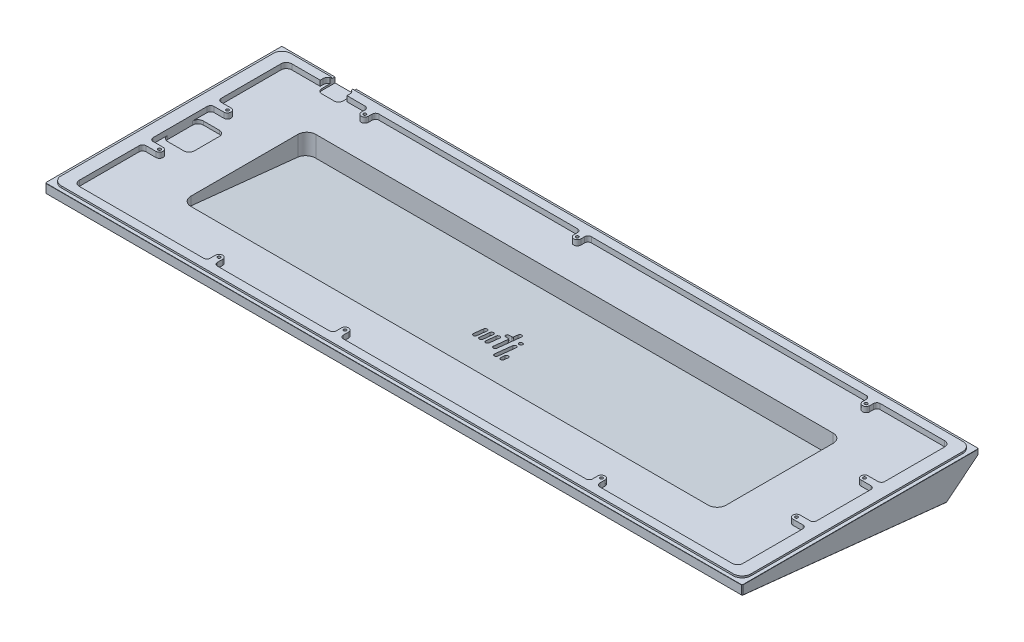
SolidWorks part; units mm, degrees
material "6061-T6 (SS)"
ref_plane "Front Plane" through (0, 0, 0) normal (0, 0, 1) x (1, 0, 0)
ref_plane "Top Plane" through (0, 0, 0) normal (0, 1, 0) x (1, 0, 0)
ref_plane "Right Plane" through (0, 0, 0) normal (1, 0, 0) x (0, 0, -1)
sketch "Sketch1" plane through (0, 0, 0) normal (0, 1, 0) x (1, 0, 0)
  line L1 (0, 0) -> (390.7, 0)
  line L2 (0, 0) -> (0, 132.7)
  line L3 (0, 132.7) -> (390.7, 132.7)
  line L4 (390.7, 0) -> (390.7, 132.7)
  dimension "D1" = 390.7
  dimension "D2" = 132.7
extrude "MainBody" add sketch "Sketch1" along normal blind 18.5
sketch "Sketch2" plane through (0, 18.5, 0) normal (0, 1, 0) x (1, 0, 0)
  line L0 (390.7, 132.7) -> (0, 132.7) construction
  line L1 (2.05, 130.65) -> (388.65, 130.65)
  line L2 (2.05, 130.65) -> (2.05, 2.05)
  line L3 (2.05, 2.05) -> (388.65, 2.05)
  line L4 (388.65, 130.65) -> (388.65, 2.05)
  line L5 (0, 132.7) -> (0, 0) construction
  line L7 (0, 132.7) -> (390.7, 132.7)
  line L8 (0, 132.7) -> (0, 0)
  line L9 (0, 0) -> (390.7, 0)
  line L10 (390.7, 132.7) -> (390.7, 0)
  point P4 (195.35, 130.65)
  point P7 (195.35, 132.7)
  point P8 (2.05, 66.35)
  point P11 (0, 66.35)
  line M5 (0, 132.7) -> (0, 0)
  line M6 (0, 0) -> (390.7, 0)
  line M7 (390.7, 0) -> (390.7, 132.7)
  line M8 (390.7, 132.7) -> (0, 132.7)
  dimension "D1" = 2.05
  dimension "D2" = 2.05
extrude "AligmentLip" cut sketch "Sketch2" against normal blind 1 contours L1 L4 L3 L2 M8 M5 M6 M7
sketch "Sketch3" plane through (0, 0, 0) normal (-1, 0, 0) x (0, 0, 1)
  line L0 (-132.7, 14.5) -> (-114.794, 0)
  line L1 (-132.7, 17.5) -> (-132.7, 0) construction
  line L2 (-132.7, 0) -> (0, 0) construction
  line L3 (-114.794, 0) -> (0, 12.0653)
  line L4 (0, 17.5) -> (0, 0) construction
  line L5 (-132.7, 17.5) -> (0, 17.5) construction
  line L7 (-132.7, 17.5) -> (0, 17.5)
  line L8 (-132.7, 17.5) -> (-132.7, 0)
  line L9 (-132.7, 0) -> (0, 0)
  line L10 (0, 17.5) -> (0, 0)
  line M4 (-132.7, 17.5) -> (-132.7, 0)
  line M5 (-132.7, 0) -> (0, 0)
  line M6 (0, 0) -> (0, 17.5)
  dimension "D1" = 6
  dimension "D2" = 135
  dimension "D3" = 3
extrude "TypingAngle" cut sketch "Sketch3" against normal through all contours L0 M4 M5 | L3 M5 M6
sketch "Sketch4" plane through (0, 18.5, 0) normal (0, 1, 0) x (1, 0, 0)
  line L0 (2.05, 130.65) -> (388.65, 130.65) construction
  line L1 (9.35, 125.9) -> (381.35, 125.9)
  line L2 (9.35, 125.9) -> (9.35, 6.8)
  line L3 (9.35, 6.8) -> (381.35, 6.8)
  line L4 (381.35, 125.9) -> (381.35, 6.8)
  line L5 (2.05, 130.65) -> (2.05, 2.05) construction
  point P4 (195.35, 125.9)
  point P7 (195.35, 130.65)
  point P8 (9.35, 66.35)
  point P11 (2.05, 66.35)
  dimension "D1" = 372
  dimension "D2" = 119.1
extrude "PCBCutout" cut sketch "Sketch4" against normal blind 3
sketch "Sketch13" plane through (0, 15.5, 0) normal (0, 1, 0) x (1, 0, 0)
  line L0 (9.35, 125.9) -> (9.35, 6.8) construction
  line L1 (9.35, 76.35) -> (24.35, 76.35)
  line L2 (9.35, 76.35) -> (9.35, 56.35)
  line L3 (9.35, 56.35) -> (24.35, 56.35)
  line L4 (24.35, 76.35) -> (24.35, 56.35)
  line L5 (2.05, 130.65) -> (2.05, 2.05) construction
  point P6 (9.35, 66.35)
  point P9 (2.05, 66.35)
  dimension "D1" = 15
  dimension "D2" = 20
extrude "Cut-Extrude4" cut sketch "Sketch13" against normal blind 2
fillet "Fillet2" radius 3 8 edges at (381.35, 17, -125.9) (381.35, 17, -6.8) (9.35, 17, -6.8) (9.35, 17, -125.9) (9.35, 14.5, -56.35) (24.35, 14.5, -56.35) (9.35, 14.5, -76.35) (24.35, 14.5, -76.35)
chamfer "Chamfer1" distance 0.5 angle 45 13 edges at (195.35, 12.0653, 0) (390.7, 16, -132.7) (0, 16, -132.7) (0, 7.25, -123.747) (390.7, 7.25, -123.747) (390.7, 6.0327, -57.397) (390.7, 14.7827, 0) (0, 6.0327, -57.397) (0, 14.7827, 0) (0, 17.5, -66.35) (195.35, 17.5, 0) (390.7, 17.5, -66.35) (195.35, 17.5, -132.7)
chamfer "Chamfer2" distance 0.1 angle 45 1 edges at (2.05, 18.5, -66.35)
sketch "Sketch17" plane through (0, 11.9335, -1.2543) normal (0, -0.9945, 0.1045) x (1, 0, 0)
  line L0 (198.25, -60.7388) -> (196.25, -60.7388) construction
  line L1 (198.25, -68.7388) -> (196.25, -68.7388)
  line L2 (198.25, -68.7388) -> (198.25, -52.7388)
  line L3 (198.25, -52.7388) -> (196.25, -52.7388)
  line L4 (196.25, -68.7388) -> (196.25, -52.7388)
  line L5 (202.75, -61.2388) -> (200.75, -61.2388)
  line L6 (202.75, -61.2388) -> (202.75, -48.7388)
  line L7 (202.75, -48.7388) -> (200.75, -48.7388)
  line L8 (200.75, -61.2388) -> (200.75, -48.7388)
  line L9 (193.45, -61.2388) -> (191.45, -61.2388)
  line L10 (193.45, -61.2388) -> (193.45, -53.2388)
  line L11 (193.45, -53.2388) -> (191.45, -53.2388)
  line L12 (191.45, -61.2388) -> (191.45, -53.2388)
  line L13 (189.95, -61.2388) -> (187.95, -61.2388)
  line L14 (189.95, -61.2388) -> (189.95, -53.2388)
  line L15 (189.95, -53.2388) -> (187.95, -53.2388)
  line L16 (187.95, -61.2388) -> (187.95, -53.2388)
  line L17 (186.45, -61.2388) -> (184.45, -61.2388)
  line L18 (186.45, -61.2388) -> (186.45, -53.2388)
  line L19 (186.45, -53.2388) -> (184.45, -53.2388)
  line L20 (184.45, -61.2388) -> (184.45, -53.2388)
  line L25 (202.75, -61.2388) -> (187.95, -61.2388) construction
  line L26 (390.2, -114.1651) -> (0.5, -114.1651) construction
  line L27 (194.25, -64.7388) -> (198.25, -64.7388)
  line L28 (194.25, -62.7388) -> (198.25, -62.7388)
  line L29 (390.7, 1.2612) -> (0, 1.2612) construction
  line L31 (206.25, -53.2388) -> (204.25, -53.2388)
  line L32 (206.25, -53.2388) -> (206.25, -48.7388)
  line L33 (206.25, -48.7388) -> (204.25, -48.7388)
  line L34 (204.25, -53.2388) -> (204.25, -48.7388)
  circle A0 centre (201.75, -63.7388) radius 1
  circle A2 centre (194.25, -63.7388) radius 1
  circle A3 centre (197.25, -67.7388) radius 1
  circle A4 centre (197.25, -53.7388) radius 1
  circle A5 centre (201.75, -60.2388) radius 1
  circle A6 centre (201.75, -49.7388) radius 1
  circle A7 centre (205.25, -52.2388) radius 1
  circle A8 centre (205.25, -49.7388) radius 1
  circle A9 centre (192.45, -60.2388) radius 1
  circle A10 centre (192.45, -54.2388) radius 1
  circle A11 centre (188.95, -60.2388) radius 1
  circle A12 centre (188.95, -54.2388) radius 1
  circle A13 centre (185.45, -60.2388) radius 1
  circle A14 centre (185.45, -54.2388) radius 1
  point P28 (195.35, -61.2388)
  point P29 (201.75, -61.2388)
  point P31 (0, 0)
  point P33 (195.35, -114.1651)
  point P44 (197.25, -68.7388)
  dimension "D12" = 2
  dimension "D13" = 12.5
  dimension "D16" = 2
  dimension "D1" = 16
  dimension "D2" = 2
  dimension "D3" = 0
  dimension "D4" = 2.5
  dimension "D5" = 2.8
  dimension "D6" = 1.5
  dimension "D7" = 1.5
  dimension "D8" = 8
  dimension "D9" = 0.5
  dimension "D10" = 1.5
  dimension "D11" = 2.5
  dimension "D14" = 4.5
  dimension "D15" = 50
  dimension "D17" = 2
  dimension "D18" = 3
  dimension "D19" = 11
extrude "Cut-Extrude5" cut sketch "Sketch17" against normal blind 10 contours A7 | A8 L34 A7 L32 | A8 | A6 | A6 L8 A5 L6 | A5 | A4 | A4 L4 L28 L2 | L28 L4 L27 L2 | A3 L2 L27 L4 | A3 | A2 L27 L4 L28 | A2 | A0 | A9 | A10 L12 A9 L10 | A10 | A12 L16 A11 L14 | A11 | A12 | A14 | A14 L20 A13 L18 | A13
sketch "Sketch18" plane through (0, 0, -132.7) normal (0, 0, -1) x (-1, 0, 0)
  line L1 (-41.8, 18.5) -> (-29.8, 18.5)
  line L2 (-41.8, 18.5) -> (-41.8, 14.5)
  line L3 (-41.8, 14.5) -> (-29.8, 14.5)
  line L4 (-29.8, 18.5) -> (-29.8, 14.5)
  line L5 (0, 17.5) -> (0, 14.7385) construction
  line L6 (-390.2, 14.5) -> (-0.5, 14.5) construction
  line L8 (-2.15, 18.5) -> (-388.65, 18.5) construction
  point P6 (-35.8, 18.5)
  dimension "D1" = 35.8
  dimension "D3" = 12
extrude "Cut-Extrude6" cut sketch "Sketch18" against normal blind 10
sketch "Sketch12" plane through (0, 18.5, 0) normal (0, 1, 0) x (1, 0, 0)
  line L0 (381.35, 125.9) -> (9.35, 125.9) construction
  line L1 (28.3, 125.9) -> (43.3, 125.9)
  line L2 (28.3, 125.9) -> (28.3, 129.85)
  line L3 (28.3, 129.85) -> (43.3, 129.85)
  line L4 (43.3, 125.9) -> (43.3, 129.85)
  line L6 (390.7, 132.7) -> (0, 132.7) construction
  line L7 (41.8, 132.7) -> (29.8, 132.7) construction
  point P6 (35.8, 129.85)
  point P11 (35.8, 132.7)
  dimension "D1" = 15
  dimension "D2" = 2.85
extrude "Cut-Extrude3" cut sketch "Sketch12" against normal up to surface (3 mm away) up to face at (92.04, 15.5, -77.94)
fillet "Fillet1" radius 2.5 4 edges at (43.3, 17, -129.85) (28.3, 17, -129.85) (41.8, 15, -122.7) (29.8, 15, -122.7)
sketch "Sketch19" plane through (0, 15.5, 0) normal (0, 1, 0) x (1, 0, 0)
  line L1 (195.35, 0) -> (195.35, 132.7) construction
  line L6 (378.35, 125.9) -> (43.3, 125.9) construction
  line L7 (55.3, 121.9) -> (59.3, 121.9)
  line L8 (55.3, 121.9) -> (55.3, 125.9)
  line L9 (55.3, 125.9) -> (59.3, 125.9)
  line L10 (59.3, 121.9) -> (59.3, 125.9)
  line L11 (378.35, 125.9) -> (43.3, 125.9) construction
  line L12 (174.4, 121.9) -> (178.4, 121.9)
  line L13 (174.4, 121.9) -> (174.4, 125.9)
  line L14 (174.4, 125.9) -> (178.4, 125.9)
  line L15 (178.4, 121.9) -> (178.4, 125.9)
  line L16 (336.3, 121.9) -> (340.3, 121.9)
  line L17 (336.3, 121.9) -> (336.3, 125.9)
  line L18 (336.3, 125.9) -> (340.3, 125.9)
  line L19 (340.3, 121.9) -> (340.3, 125.9)
  line L20 (381.35, 9.8) -> (381.35, 122.9) construction
  line L21 (373.9, 87.4) -> (381.35, 87.4)
  line L22 (373.9, 87.4) -> (373.9, 83.4)
  line L23 (373.9, 83.4) -> (381.35, 83.4)
  line L24 (381.35, 87.4) -> (381.35, 83.4)
  line L25 (12.35, 6.8) -> (378.35, 6.8) construction
  line L26 (373.9, 49.3) -> (381.35, 49.3)
  line L27 (373.9, 49.3) -> (373.9, 45.3)
  line L28 (373.9, 45.3) -> (381.35, 45.3)
  line L29 (381.35, 49.3) -> (381.35, 45.3)
  line L30 (298.2, 11.6) -> (302.2, 11.6)
  line L31 (298.2, 11.6) -> (298.2, 6.8)
  line L32 (298.2, 6.8) -> (302.2, 6.8)
  line L33 (302.2, 11.6) -> (302.2, 6.8)
  line L34 (12.35, 6.8) -> (378.35, 6.8) construction
  line L35 (158.5, 11.6) -> (154.5, 11.6)
  line L36 (158.5, 11.6) -> (158.5, 6.8)
  line L37 (158.5, 6.8) -> (154.5, 6.8)
  line L38 (154.5, 11.6) -> (154.5, 6.8)
  line L39 (9.35, 59.35) -> (9.35, 9.8) construction
  line L40 (87.9, 11.6) -> (83.9, 11.6)
  line L41 (87.9, 11.6) -> (87.9, 6.8)
  line L42 (87.9, 6.8) -> (83.9, 6.8)
  line L43 (83.9, 11.6) -> (83.9, 6.8)
  line L44 (16.8, 49.3) -> (9.35, 49.3)
  line L45 (16.8, 49.3) -> (16.8, 45.3)
  line L46 (16.8, 45.3) -> (9.35, 45.3)
  line L47 (9.35, 49.3) -> (9.35, 45.3)
  line L48 (9.35, 122.9) -> (9.35, 9.8) construction
  line L49 (16.8, 87.4) -> (9.35, 87.4)
  line L50 (16.8, 87.4) -> (16.8, 83.4)
  line L51 (16.8, 83.4) -> (9.35, 83.4)
  line L52 (9.35, 87.4) -> (9.35, 83.4)
  line L53 (390.2, 132.7) -> (41.8, 132.7) construction
  line L54 (0, 132.2) -> (0, 0.5) construction
  line L55 (0.5, 0) -> (390.2, 0) construction
  circle A0 centre (57.3, 121.9) radius 2
  circle A1 centre (176.4, 121.9) radius 2
  circle A2 centre (338.3, 121.9) radius 2
  circle A3 centre (16.8, 85.4) radius 2
  circle A4 centre (16.8, 47.3) radius 2
  circle A5 centre (85.9, 11.6) radius 2
  circle A6 centre (156.5, 11.6) radius 2
  circle A7 centre (300.2, 11.6) radius 2
  circle A8 centre (373.9, 85.4) radius 2
  circle A9 centre (373.9, 47.3) radius 2
  dimension "D2" = 4
  dimension "D6" = 4
  dimension "D12" = 4
  dimension "D3" = 57.3
  dimension "D4" = 119.1
  dimension "D5" = 161.9
  dimension "D7" = 40.5
  dimension "D8" = 38.1
  dimension "D9" = 36.5
  dimension "D10" = 110.3
  dimension "D11" = 28.6
  dimension "D13" = 70.6
  dimension "D14" = 143.7
  dimension "D15" = 10.8
extrude "Boss-Extrude1" add sketch "Sketch19" along normal up to surface (3 mm away) contours L46 L47 L44 L45 | L51 L52 L49 L50 | A4 | A3 | L10 L9 L8 L7 | A0 | L15 L14 L13 L12 | A1 | L19 L18 L17 L16 | A2 | L21 L24 L23 L22 | A8 | L26 L29 L28 L27 | A9 | L33 L32 L31 L30 | A7 | L36 L37 L38 L35 | A6 | L41 L42 L43 L40 | A5 up to face at (131.54, 18.5, -91.2282)
fillet "Fillet3" radius 1.9 20 edges at (83.9, 17, -6.8) (87.9, 17, -6.8) (158.5, 17, -6.8) (154.5, 17, -6.8) (298.2, 17, -6.8) (302.2, 17, -6.8) (381.35, 17, -45.3) (381.35, 17, -49.3) (381.35, 17, -87.4) (381.35, 17, -83.4) (336.3, 17, -125.9) (340.3, 17, -125.9) (178.4, 17, -125.9) (174.4, 17, -125.9) (59.3, 17, -125.9) (55.3, 17, -125.9) (9.35, 17, -87.4) (9.35, 17, -49.3) (9.35, 17, -45.3) (9.35, 17, -83.4)
sketch "Sketch20" plane through (0, 18.5, 0) normal (0, 1, 0) x (1, 0, 0)
  point P0 (16.8, 47.3)
  point P1 (16.8, 85.4)
  point P3 (85.9, 11.6)
  point P5 (156.5, 11.6)
  point P7 (300.2, 11.6)
  point P9 (373.9, 47.3)
  point P11 (373.9, 85.4)
  point P13 (338.3, 121.9)
  point P15 (176.4, 121.9)
  point P17 (57.3, 121.9)
hole_wizard "M2x0.4 Tapped Hole1" positions "3DSketch3" profile "Sketch22" tap size "M2x0.4" standard "ANSI Metric"
sketch3d "3DSketch3"
  point P0 (57.3, 18.5, -121.9)
  point P3 (176.4, 18.5, -121.9)
  point P6 (16.8, 18.5, -47.3)
  point P9 (16.8, 18.5, -85.4)
  point P12 (85.9, 18.5, -11.6)
  point P15 (156.5, 18.5, -11.6)
  point P18 (300.2, 18.5, -11.6)
  point P21 (373.9, 18.5, -47.3)
  point P24 (373.9, 18.5, -85.4)
  point P27 (338.3, 18.5, -121.9)
sketch "Sketch22" plane through (57.3, 18.5, -121.9) normal (1, 0, 0) x (0, 0, 1)
  line L0 (0, 0) -> (0, 4.4807)
  line L1 (0, 4.4807) -> (0.8, 4)
  line L2 (0.8, 4) -> (0.8, 0)
  line L5 (0.8, 0) -> (0, 0)
  line L10 (0, 4.4807) -> (-0.8, 4) construction
  line L11 (0, -6.35) -> (0, 107.95) construction
  dimension "Tap Drill Dia." = 1.6
  dimension "Tap Drill Depth" = 4
  dimension "Drill Angle" = 118
cosmetic thread "Hole Thread1" parameters "D1"=4, "D2"=2
cosmetic thread "Hole Thread2" parameters "D1"=4, "D2"=2
cosmetic thread "Hole Thread3" parameters "D1"=4, "D2"=2
cosmetic thread "Hole Thread4" parameters "D1"=4, "D2"=2
cosmetic thread "Hole Thread5" parameters "D1"=4, "D2"=2
cosmetic thread "Hole Thread6" parameters "D1"=4, "D2"=2
cosmetic thread "Hole Thread7" parameters "D1"=4, "D2"=2
cosmetic thread "Hole Thread8" parameters "D1"=4, "D2"=2
cosmetic thread "Hole Thread9" parameters "D1"=4, "D2"=2
cosmetic thread "Hole Thread10" parameters "D1"=4, "D2"=2
chamfer "Chamfer3" distance 0.1 angle 45 5 edges at (390.7, 17.5, -66.35) (216, 17.5, -132.7) (15.15, 17.5, -132.7) (195.35, 17.5, 0) (0, 17.5, -66.35)
fillet "Fillet4" radius 5 4 edges at (388.65, 18, -2.05) (388.65, 18, -130.65) (2.05, 17.95, -2.05) (2.05, 17.95, -130.65)
sketch "Sketch23" plane through (0, 15.5, 0) normal (0, 1, 0) x (1, 0, 0)
  line L0 (0.4, 0.1) -> (390.3, 0.1) construction
  line L1 (45.35, 101.35) -> (345.35, 101.35)
  line L2 (45.35, 101.35) -> (45.35, 31.35)
  line L3 (45.35, 31.35) -> (345.35, 31.35)
  line L4 (345.35, 101.35) -> (345.35, 31.35)
  line L5 (0.1, 132.3) -> (0.1, 0.4) construction
  point P4 (195.35, 31.35)
  point P7 (195.35, 0.1)
  point P8 (45.35, 66.35)
  point P11 (0.1, 66.35)
  dimension "D1" = 70
  dimension "D2" = 300
extrude "Cut-Extrude7" cut sketch "Sketch23" against normal offset from surface (11.5732 mm away) 2.5
fillet "Fillet5" radius 5 4 edges at (345.35, 13.392, -31.35) (345.35, 9.7134, -101.35) (45.35, 13.392, -31.35) (45.35, 9.7134, -101.35)
fillet "Fillet6" radius 0.5 2 edges at (196.25, 6.4096, -65.7691) (196.25, 6.6187, -63.7801)
